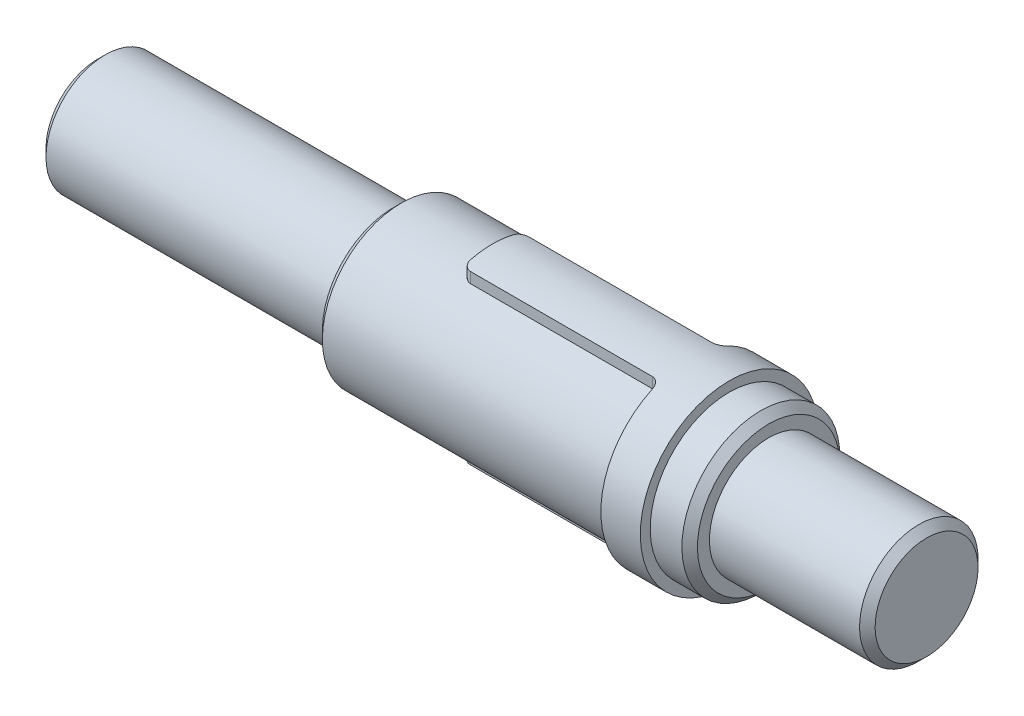
SolidWorks part; units mm, degrees
material "Stainless Steel (ferritic)"
ref_plane "Front Plane" through (0, 0, 0) normal (0, 0, 1) x (1, 0, 0)
ref_plane "Top Plane" through (0, 0, 0) normal (0, 1, 0) x (1, 0, 0)
ref_plane "Right Plane" through (0, 0, 0) normal (1, 0, 0) x (0, 0, -1)
sketch "Sketch1" plane through (0, 0, 0) normal (0, 0, 1) x (1, 0, 0)
  line L0 (-381, 4.1994) -> (-381, 80.3994)
  line L1 (-381, 80.3994) -> (0, 80.3994)
  line L2 (0, 80.3994) -> (0, 105.7994)
  line L3 (0, 105.7994) -> (127, 105.7994)
  line L4 (127, 105.7994) -> (127, 118.4994)
  line L5 (127, 118.4994) -> (431.8, 118.4994)
  line L6 (431.8, 118.4994) -> (431.8, 105.7994)
  line L7 (431.8, 105.7994) -> (482.6, 105.7994)
  line L8 (482.6, 105.7994) -> (482.6, 80.3994)
  line L9 (482.6, 80.3994) -> (685.8, 80.3994)
  line L10 (685.8, 80.3994) -> (685.8, 4.1994)
  line L11 (685.8, 4.1994) -> (-381, 4.1994)
  point P2 (0, 0)
  dimension "D1" = 381
  dimension "D2" = 127
  dimension "D3" = 304.8
  dimension "D4" = 50.8
  dimension "D5" = 1066.8
  dimension "D6" = 76.2
  dimension "D7" = 1066.8
  dimension "D8" = 25.4
  dimension "D9" = 12.7
  dimension "D10" = 25.4
  dimension "D11" = 76.2
revolve "Revolve4" add sketch "Sketch1" angle 360 about L11
sketch "Sketch3" plane through (127, 0, 0) normal (-1, 0, 0) x (0, 0, 1)
  line L1 (-38.1, -186.3006) -> (38.1, -186.3006)
  line L2 (-38.1, -186.3006) -> (-38.1, 194.6994)
  line L3 (-38.1, 194.6994) -> (38.1, 194.6994)
  line L4 (38.1, -186.3006) -> (38.1, 194.6994)
  line L5 (-38.1, -186.3006) -> (38.1, 194.6994) construction
  line L6 (-38.1, 194.6994) -> (38.1, -186.3006) construction
  circle A0 centre (0, 4.1994) radius 177.8
  circle A1 centre (0, 4.1994) radius 127
  point P0 (0, 4.1994)
  circle M4 centre (0, 4.1994) radius 101.6
  circle M5 centre (0, 4.1994) radius 114.3
  dimension "D3" = 254
  dimension "D1" = 76.2
  dimension "D2" = 381
extrude "Cut-Extrude1" cut sketch "Sketch3" against normal blind 254 contours L4 M5 M4 | L2 M5 M4 region at (127, 4.1994, -112.014) region at (127, -96.775, 40.386)
chamfer "Chamfer1" distance 10 angle 45 1 edges at (685.8, 80.3994, 0)
chamfer "Chamfer2" distance 10 angle 45 1 edges at (482.6, 105.7994, 0)
chamfer "Chamfer3" distance 10 angle 45 1 edges at (-381, 80.3994, 0)
chamfer "Chamfer4" distance 10 angle 45 1 edges at (0, 105.7994, 0)
fillet "Fillet1" radius 10 8 edges at (127, -96.775, 38.1) (381, -96.775, 38.1) (127, -96.775, -38.1) (381, -96.775, -38.1) (381, 105.1738, -38.1) (127, 105.1738, -38.1) (381, 105.1738, 38.1) (127, 105.1738, 38.1)
